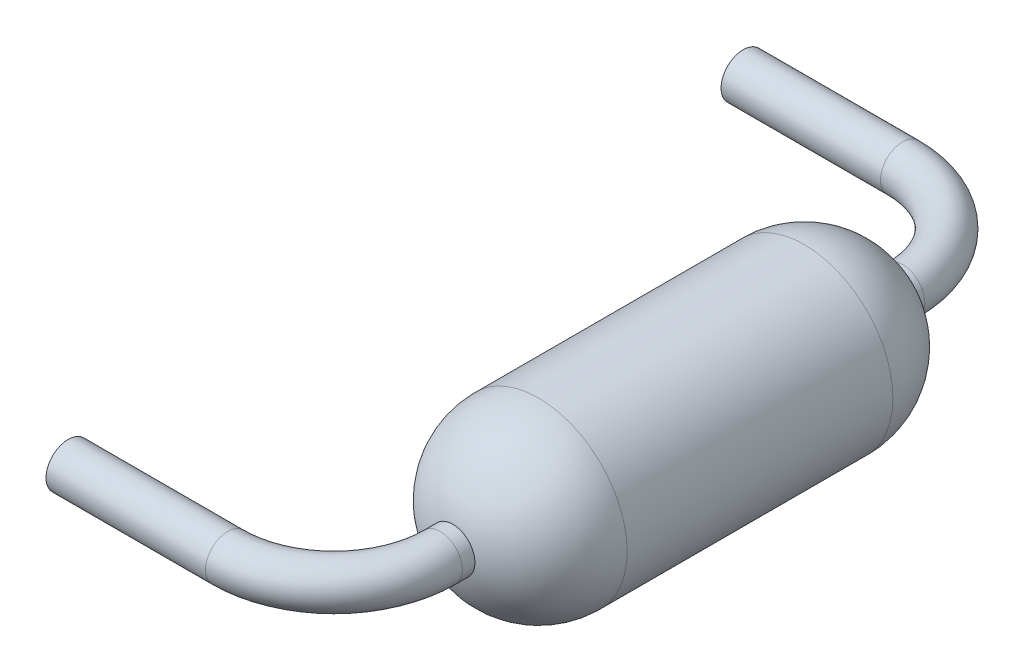
SolidWorks part; units mm, degrees
ref_plane "Front Plane" through (0, 0, 0) normal (0, 0, 1) x (1, 0, 0)
ref_plane "Top Plane" through (0, 0, 0) normal (0, 1, 0) x (1, 0, 0)
ref_plane "Right Plane" through (0, 0, 0) normal (1, 0, 0) x (0, 0, -1)
sketch "Sketch1" plane through (0, 0, 0) normal (0, 0, 1) x (1, 0, 0)
  circle A0 centre (0, 0) radius 1
  dimension "D1" = 2
extrude "Boss-Extrude1" add sketch "Sketch1" along normal mid plane 3
dome "Dome1" faces to dome 1 distance 1 reverse direction no elliptical dome no face at (1, 0, 1.5) parameters "D1"=1
dome "Dome2" faces to dome 1 distance 1 reverse direction no elliptical dome no face at (1, 0, -1.5) parameters "D1"=1
sketch "Sketch3" plane through (0, 0, 0) normal (0, 1, 0) x (1, 0, 0)
  line L0 (0, -2.61) -> (0, 2.61)
  line L1 (-1.2, -3.81) -> (-3, -3.81)
  line L2 (-1.2, 3.81) -> (-3, 3.81)
  arc A0 (0, 2.61) -> (-1.2, 3.81) centre (-1.2, 2.61) ccw
  arc A1 (0, -2.61) -> (-1.2, -3.81) centre (-1.2, -2.61) cw
  point P4 (0, 0)
  point P9 (0, 3.81)
  point P12 (0, -3.81)
  dimension "D3" = 1.2
  dimension "D1" = 7.62
  dimension "D2" = 3
sketch "Sketch4" plane through (0, 0, 0) normal (0, 0, 1) x (1, 0, 0)
  circle A0 centre (0, 0) radius 0.25
  dimension "D1" = 0.5
sweep "Sweep1" add profiles "Sketch4" path "Sketch3"
